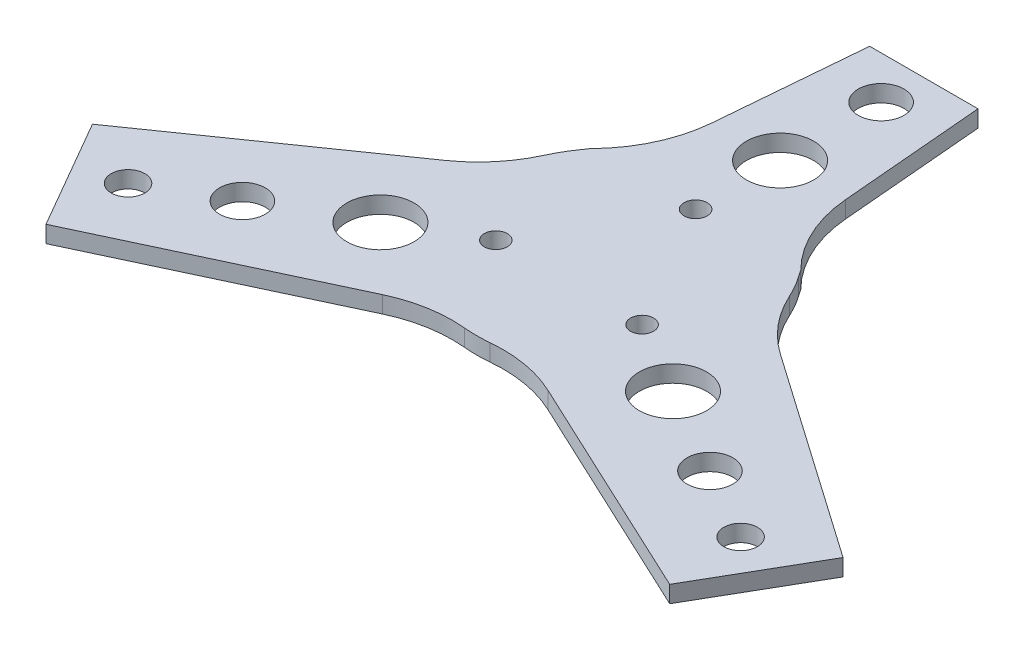
SolidWorks part; units mm, degrees
ref_plane "Front Plane" through (0, 0, 0) normal (0, 0, 1) x (1, 0, 0)
ref_plane "Top Plane" through (0, 0, 0) normal (0, 1, 0) x (1, 0, 0)
ref_plane "Right Plane" through (0, 0, 0) normal (1, 0, 0) x (0, 0, -1)
sketch "Esboço1" plane through (0, 0, 0) normal (0, 1, 0) x (1, 0, 0)
  line L0 (0, -91.9719) -> (0, 91.9719) construction
  line L1 (-21.75, -12.5574) -> (0, 25.1147) construction
  line L2 (0, 25.1147) -> (21.75, -12.5574) construction
  line L3 (21.75, -12.5574) -> (18.325, -12.5574) construction
  line L4 (0, 0) -> (0, 25.1147) construction
  line L5 (0, 0) -> (-21.75, -12.5574) construction
  line L6 (0, 0) -> (21.75, -12.5574) construction
  line L7 (-18.325, -12.5574) -> (-21.75, -12.5574) construction
  line L8 (18.325, -12.5574) -> (-18.325, -12.5574) construction
  line L9 (0, 25.1147) -> (0, 28.5397) construction
  line L10 (0, 40.2397) -> (0, 60.2397) construction
  line L11 (0, 28.5397) -> (0, 40.2397) construction
  line L12 (0, 73.4897) -> (0, 80.2897) construction
  line L13 (0, 60.2397) -> (0, 73.4897) construction
  line L14 (0, 80.2897) -> (0, 87.0897) construction
  line L15 (0, 100.1897) -> (0, 105.1897) construction
  line L16 (0, 87.0897) -> (0, 100.1897) construction
  line L17 (24.7161, -14.2699) -> (34.8486, -20.1199) construction
  line L18 (86.7669, -50.0949) -> (91.097, -52.5949) construction
  line L19 (75.4219, -43.5449) -> (86.7669, -50.0949) construction
  line L20 (63.644, -36.7449) -> (69.533, -40.1449) construction
  line L21 (69.533, -40.1449) -> (75.4219, -43.5449) construction
  line L22 (52.1691, -30.1199) -> (63.644, -36.7449) construction
  line L23 (34.8486, -20.1199) -> (52.1691, -30.1199) construction
  line L24 (-24.7161, -14.2699) -> (-34.8486, -20.1199) construction
  line L25 (-86.7669, -50.0949) -> (-91.097, -52.5949) construction
  line L26 (-75.4219, -43.5449) -> (-86.7669, -50.0949) construction
  line L27 (-63.644, -36.7449) -> (-69.533, -40.1449) construction
  line L28 (-69.533, -40.1449) -> (-75.4219, -43.5449) construction
  line L29 (-52.1691, -30.1199) -> (-63.644, -36.7449) construction
  line L30 (-34.8486, -20.1199) -> (-52.1691, -30.1199) construction
  circle A0 centre (-21.75, -12.5574) radius 3.425
  circle A1 centre (21.75, -12.5574) radius 3.425
  circle A2 centre (0, 25.1147) radius 3.425
  circle A3 centre (0, 50.2397) radius 10
  circle A4 centre (0, 80.2897) radius 6.8
  circle A5 centre (0, 105.1897) radius 5
  circle A6 centre (43.5089, -25.1199) radius 10
  circle A7 centre (69.533, -40.1449) radius 6.8
  circle A8 centre (91.097, -52.5949) radius 5
  circle A9 centre (-43.5089, -25.1199) radius 10
  circle A10 centre (-69.533, -40.1449) radius 6.8
  circle A11 centre (-91.097, -52.5949) radius 5
  point P51 (0, 0)
  dimension "D3" = 6.85
  dimension "D5" = 20
  dimension "D7" = 13.6
  dimension "D9" = 10
  dimension "D1" = 120
  dimension "D2" = 120
  dimension "D4" = 36.65
  dimension "D6" = 11.7
  dimension "D8" = 13.25
  dimension "D10" = 13.1
  dimension "D11" = 3
sketch "Esboço2" plane through (0, 0, 0) normal (0, 1, 0) x (1, 0, 0)
  line L0 (-19.975, 105.1897) -> (-24.695, 50.2397) construction
  line L1 (0, 0) -> (0, 105.1897) construction
  line L2 (0, 105.1897) -> (-19.975, 105.1897) construction
  line L3 (-24.695, 50.2397) -> (0, 50.2397) construction
  line L4 (-18.8746, 118) -> (-25.3192, 42.9723)
  line L5 (18.8746, 118) -> (25.3192, 42.9723)
  line L6 (-18.8746, 118) -> (18.8746, 118)
  line L7 (111.6283, -42.6541) -> (49.8747, 0.441)
  line L8 (111.6283, -42.6541) -> (92.7537, -75.3459)
  line L9 (92.7537, -75.3459) -> (24.5555, -43.4133)
  line L10 (-92.7537, -75.3459) -> (-24.5555, -43.4133)
  line L11 (-92.7537, -75.3459) -> (-111.6283, -42.6541)
  line L12 (-111.6283, -42.6541) -> (-49.8747, 0.441)
  arc A0 (-3.7967, -39.8194) -> (3.7967, -39.8194) centre (0, 0) ccw
  arc A1 (36.383, 16.6216) -> (32.5862, 23.1978) centre (0, 0) ccw
  arc A2 (-32.5862, 23.1978) -> (-36.383, 16.6216) centre (0, 0) ccw
  arc A3 (25.3192, 42.9723) -> (32.5862, 23.1978) centre (65.1725, 46.3955) ccw
  arc A4 (49.8747, 0.441) -> (36.383, 16.6216) centre (72.766, 33.2433) cw
  arc A5 (24.5555, -43.4133) -> (3.7967, -39.8194) centre (7.5935, -79.6388) ccw
  arc A6 (-24.5555, -43.4133) -> (-3.7967, -39.8194) centre (-7.5935, -79.6388) cw
  arc A7 (-49.8747, 0.441) -> (-36.383, 16.6216) centre (-72.766, 33.2433) ccw
  arc A8 (-25.3192, 42.9723) -> (-32.5862, 23.1978) centre (-65.1725, 46.3955) cw
  circle A9 centre (-91.097, -52.5949) radius 5 construction
  circle A10 centre (-69.533, -40.1449) radius 6.8 construction
  circle A11 centre (-43.5089, -25.1199) radius 10 construction
  circle A12 centre (91.097, -52.5949) radius 5 construction
  circle A13 centre (69.533, -40.1449) radius 6.8 construction
  circle A14 centre (43.5089, -25.1199) radius 10 construction
  circle A15 centre (21.75, -12.5574) radius 3.425 construction
  circle A16 centre (-21.75, -12.5574) radius 3.425 construction
  circle A17 centre (0, 25.1147) radius 3.425 construction
  circle A18 centre (0, 50.2397) radius 10 construction
  circle A19 centre (0, 80.2897) radius 6.8 construction
  circle A20 centre (0, 105.1897) radius 5 construction
  circle A21 centre (-91.097, -52.5949) radius 5
  circle A22 centre (-69.533, -40.1449) radius 6.8
  circle A23 centre (-43.5089, -25.1199) radius 10
  circle A24 centre (91.097, -52.5949) radius 5
  circle A25 centre (69.533, -40.1449) radius 6.8
  circle A26 centre (43.5089, -25.1199) radius 10
  circle A27 centre (21.75, -12.5574) radius 3.425
  circle A28 centre (-21.75, -12.5574) radius 3.425
  circle A29 centre (0, 25.1147) radius 3.425
  circle A30 centre (0, 50.2397) radius 10
  circle A31 centre (0, 80.2897) radius 6.8
  circle A32 centre (0, 105.1897) radius 5
  point P25 (0, 0)
  point P26 (26.4316, 30.0229)
  point P37 (-26.4316, 30.0229)
  dimension "D1" = 80
  dimension "D6" = 40
  dimension "D2" = 39.95
  dimension "D3" = 49.39
  dimension "D4" = 118
  dimension "D5" = 3
extrude "Ressalto-extrusão1" add sketch "Esboço2" along normal blind 5
sketch "Esboço3" plane through (0, 0, 0) normal (0, 1, 0) x (1, 0, 0)
  line L0 (-16.11, 93) -> (-19.8151, 49.8655)
  line L5 (-18.8746, 118) -> (-25.3192, 42.9723) construction
  line L6 (16.11, 93) -> (19.8151, 49.8655)
  line L7 (18.8746, 118) -> (25.3192, 42.9723) construction
  line L10 (-16.11, 93) -> (16.11, 93)
  line L11 (0, 0) -> (0, 105.1897) construction
  line L12 (-59.6683, 13.2887) -> (-59.6683, 140.1547)
  line L13 (-59.6683, 140.1547) -> (59.6683, 140.1547)
  line L14 (59.6683, 140.1547) -> (59.6683, 13.2887)
  arc A1 (-59.6683, 13.2887) -> (-19.8151, 49.8655) centre (-59.6683, 53.2887) ccw
  arc A2 (-49.8747, 0.441) -> (-36.383, 16.6216) centre (-72.766, 33.2433) ccw construction
  arc A3 (19.8151, 49.8655) -> (59.6683, 13.2887) centre (59.6683, 53.2887) ccw
  arc A4 (-32.5862, 23.1978) -> (-36.383, 16.6216) centre (0, 0) ccw construction
  arc A5 (36.383, 16.6216) -> (32.5862, 23.1978) centre (0, 0) ccw construction
  point P16 (0, 93)
  dimension "D1" = 93
  dimension "D2" = 32.22
extrude "Corte-extrusão4" cut sketch "Esboço3" along normal blind 5
